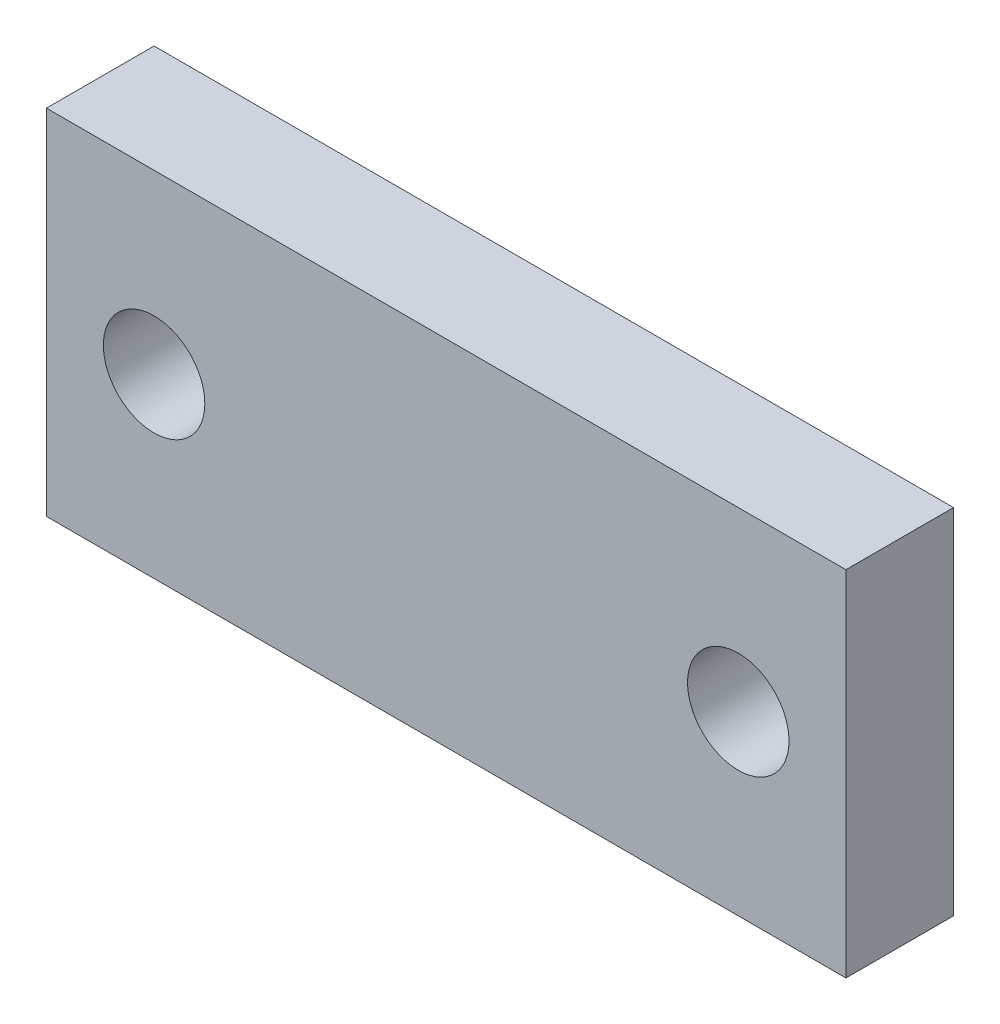
SolidWorks part; units mm, degrees
ref_plane "Front" through (0, 0, 0) normal (0, 0, 1) x (1, 0, 0)
ref_plane "Top" through (0, 0, 0) normal (0, 1, 0) x (1, 0, 0)
ref_plane "Right" through (0, 0, 0) normal (1, 0, 0) x (0, 0, -1)
sketch "草图1" plane through (0, 0, 0) normal (0, 0, 1) x (1, 0, 0)
  line L1 (-26, -11.5) -> (26, -11.5)
  line L2 (-26, -11.5) -> (-26, 11.5)
  line L3 (-26, 11.5) -> (26, 11.5)
  line L4 (26, -11.5) -> (26, 11.5)
  line L5 (-26, -11.5) -> (26, 11.5) construction
  line L6 (-26, 11.5) -> (26, -11.5) construction
  point P0 (0, 0)
  dimension "D1" = 52
  dimension "D2" = 23
extrude "凸台-拉伸1" add sketch "草图1" along normal blind 7
sketch "草图2" plane through (0, 0, 7) normal (0, 0, 1) x (1, 0, 0)
  line L1 (-26, 11.5) -> (-26, -11.5) construction
  line L2 (26, -11.5) -> (26, 11.5) construction
  line L3 (26, 11.5) -> (-26, 11.5) construction
  point P0 (-19, 0)
  point P1 (19, 0)
  dimension "D1" = 7
  dimension "D2" = 7
  dimension "D3" = 11.5
  dimension "D4" = 11.5
hole_wizard "Ø6.6 (6.6) 直径孔1" positions "草图5" profile "草图6" hole size "Ø6.6" standard "GB" end condition up to next
sketch "草图5" plane through (0, 0, 7) normal (0, 0, 1) x (1, 0, 0)
  point P0 (-19, 0)
  point P3 (19, 0)
sketch "草图6" plane through (-19, 0, 7) normal (1, 0, 0) x (0, -1, 0)
  line L0 (0, 0) -> (0, 7)
  line L1 (0, 7) -> (3.3, 7)
  line L2 (3.3, 7) -> (3.3, 0)
  line L5 (3.3, 0) -> (0, 0)
  line L11 (0, -6.35) -> (0, 107.95) construction
  dimension "通孔孔直径" = 6.6
  dimension "通孔孔深度" = 7
